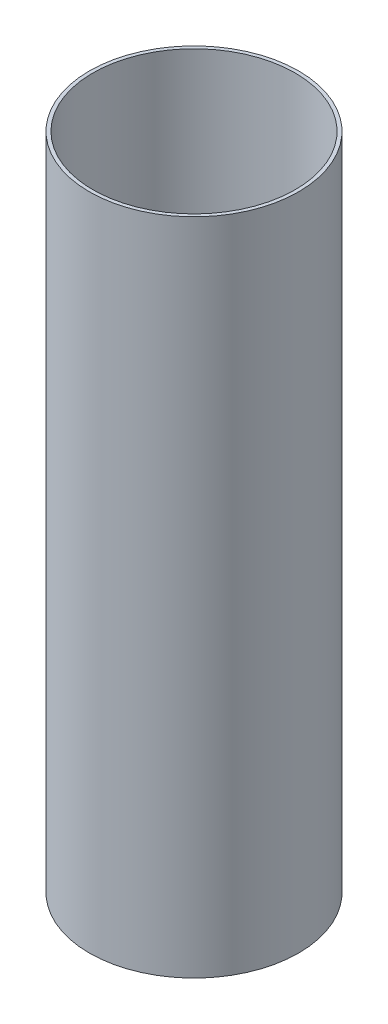
SolidWorks part; units mm, degrees
material "PC High Viscosity"
ref_plane "Front Plane" through (0, 0, 0) normal (0, 0, 1) x (1, 0, 0)
ref_plane "Top Plane" through (0, 0, 0) normal (0, 1, 0) x (1, 0, 0)
ref_plane "Right Plane" through (0, 0, 0) normal (1, 0, 0) x (0, 0, -1)
sketch "Sketch1" plane through (0, 0, 0) normal (0, 0, 1) x (1, 0, 0)
  line L0 (0, 0) -> (0, 600) construction
  line L1 (95.25, 0) -> (92.075, 0)
  line L2 (95.25, 600) -> (95.25, 0)
  line L3 (92.075, 0) -> (92.075, 600)
  line L4 (92.075, 600) -> (95.25, 600)
  line L5 (0, 600) -> (92.075, 600) construction
  line L6 (0, 0) -> (92.075, 0) construction
  dimension "D1" = 92.075
  dimension "D2" = 3.175
  dimension "D3" = 600
revolve "Revolve1" add sketch "Sketch1" angle 360 about L0
ref_plane "Plane1" through (0, 0, 101) normal (0, 0, 1) x (1, 0, 0)
ref_plane "Plane2" through (95.25, 0, 0) normal (1, 0, 0) x (0, 0, -1)
sketch "Sketch3" plane through (95.25, 0, 0) normal (1, 0, 0) x (0, 0, -1)
  line L0 (92.075, 600) -> (-92.075, 600) construction
  circle A0 centre (0, 580.95) radius 3.175
  dimension "D1" = 19.05
  dimension "D2" = 6.35
extrude "Cut-Extrude1" [suppressed] cut sketch "Sketch3" against normal up to surface (3.2298 mm away) up to face at (0, 0, -92.075)
pattern_circular "CirPattern1" [suppressed] count 2 every 180 of bodies 106
ref_plane "Plane3" through (-95.25, 0, 0) normal (-1, 0, 0) x (0, 0, 1)
